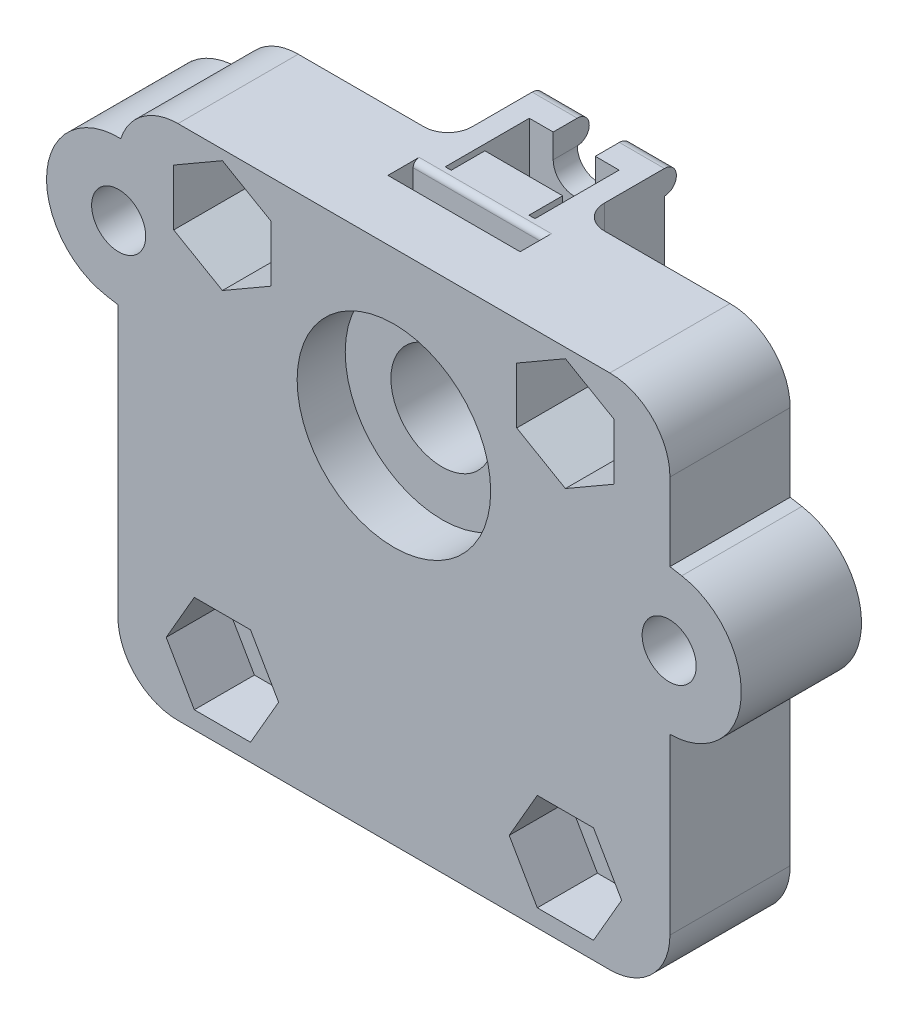
SolidWorks part; units mm, degrees
ref_plane "Front Plane" through (0, 0, 0) normal (0, 0, 1) x (1, 0, 0)
ref_plane "Top Plane" through (0, 0, 0) normal (0, 1, 0) x (1, 0, 0)
ref_plane "Right Plane" through (0, 0, 0) normal (1, 0, 0) x (0, 0, -1)
sketch "Sketch1" plane through (0, 0, 0) normal (0, 1, 0) x (1, 0, 0)
  line L0 (0, 0) -> (-22.961, -55.4328)
  line L1 (0, 0) -> (22.961, -55.4328)
  line L2 (0, 0) -> (0, -29.5283) construction
  circle A0 centre (0, 0) radius 60
  circle A1 centre (0, 0) radius 55
  circle A2 centre (0, 0) radius 50
  circle A3 centre (0, 0) radius 45
  dimension "D1" = 120
  dimension "D2" = 5
  dimension "D3" = 5
  dimension "D4" = 5
  dimension "D5" = 45
extrude "Boss-Extrude1" add sketch "Sketch1" along normal mid plane 27 contours A1 L0 A0 L1 | A2 L0 A1 L1 | A3 L0 A2 L1 region at (0, 0, 46.3313) region at (0, 0, 51.1997) region at (0, 0, 56.0688)
extrude "Boss-Extrude2" add sketch "Sketch1<3>" along normal mid plane 37 contours A2 L0 A1 L1 region at (0, 0, 51.1997)
sketch "Sketch1<3>" plane through (0, 0, 0) normal (0, 1, 0) x (1, 0, 0) same geometry as "Sketch1"
ref_plane "Plane1" through (0, 0, 60) normal (0, 0, 1) x (1, 0, 0)
sketch "Sketch3" plane through (0, 0, 0) normal (0, -1, 0) x (1, 0, 0)
  line L0 (-22.961, 55.4328) -> (-22.961, 266)
  line L1 (-22.961, 266) -> (22.961, 266)
  line L2 (22.961, 266) -> (22.961, 55.4328)
  line L3 (-17.961, 57.2486) -> (-17.961, 246)
  line L4 (-17.961, 246) -> (17.961, 246)
  line L5 (17.961, 246) -> (17.961, 57.2486)
  arc A0 (22.961, 55.4328) -> (-22.961, 55.4328) centre (0, 0) ccw construction
  arc A1 (22.961, 55.4328) -> (-22.961, 55.4328) centre (0, 0) ccw
  dimension "D1" = 5
  dimension "D2" = 5
  dimension "D3" = 20
  dimension "D4" = 266
extrude "Boss-Extrude3" add sketch "Sketch3" against normal mid plane 10 contours L3 A1 L0 L1 L2 L5 L4 region at (-20.8058, 0, 160.7164)
sketch "Sketch4" plane through (0, 0, 0) normal (0, 1, 0) x (1, 0, 0)
  line L0 (22.961, -266) -> (22.961, -55.4328) construction
  line L1 (-22.961, -266) -> (22.961, -266)
  line L2 (-22.961, -266) -> (-22.961, -246)
  line L3 (-22.961, -246) -> (22.961, -246)
  line L4 (22.961, -266) -> (22.961, -246)
  line L5 (-17.961, -246) -> (17.961, -246) construction
extrude "Boss-Extrude4" add sketch "Sketch4" along normal mid plane 27
sketch "Sketch2" plane through (0, 0, 0) normal (0, 0, 1) x (1, 0, 0)
  circle A0 centre (0, 0) radius 4.25
  dimension "D1" = 8.5
extrude "Cut-Extrude1" cut sketch "Sketch2" along normal through all
sketch "Sketch6" plane through (0, 0, 266) normal (0, 0, 1) x (1, 0, 0)
  circle A0 centre (0, 0) radius 8.05
  dimension "D1" = 16.1
extrude "Cut-Extrude3" cut sketch "Sketch6" against normal blind 14
sketch "Sketch9" plane through (0, 0, 0) normal (0, 1, 0) x (1, 0, 0)
  line L0 (-22.961, -55.4328) -> (-22.961, -68)
  line L1 (-22.961, -55.4328) -> (-22.961, -246) construction
  line L2 (-22.961, -68) -> (22.961, -68)
  line L3 (22.961, -246) -> (22.961, -55.4328) construction
  line L4 (22.961, -68) -> (22.961, -55.4328)
  arc A0 (-22.961, -55.4328) -> (22.961, -55.4328) centre (0, 0) ccw construction
  arc A1 (-22.961, -55.4328) -> (22.961, -55.4328) centre (0, 0) ccw
  point P3 (0, -60)
  dimension "D1" = 8
extrude "Boss-Extrude5" add sketch "Sketch9" along normal mid plane 27
sketch "Sketch8" plane through (0, 0, 60) normal (0, 0, 1) x (1, 0, 0)
  circle A0 centre (0, 0) radius 9
  dimension "D1" = 18
extrude "Cut-Extrude5" cut sketch "Sketch8" against normal up to next
sketch "Sketch10" plane through (0, 0, 60) normal (0, 0, 1) x (1, 0, 0)
  circle A0 centre (0, 0) radius 4
  dimension "D1" = 8
extrude "Cut-Extrude6" cut sketch "Sketch10" along normal up to next
sketch "Sketch11" plane through (0, 0, 68) normal (0, 0, 1) x (1, 0, 0)
  circle A0 centre (0, 0) radius 8
  dimension "D1" = 16
extrude "Cut-Extrude7" cut sketch "Sketch11" against normal blind 4
sketch "Sketch18" plane through (0, 0, 0) normal (0, 0, 1) x (1, 0, 0)
  circle A0 centre (0, 0) radius 11
  dimension "D1" = 22
extrude "Cut-Extrude9" cut sketch "Sketch18" along normal blind 47
sketch "Sketch19" plane through (0, 0, 0) normal (0, 1, 0) x (1, 0, 0)
  line L1 (-22.961, -68) -> (22.961, -68)
  line L2 (-22.961, -68) -> (-22.961, -266)
  line L3 (-22.961, -266) -> (22.961, -266)
  line L4 (22.961, -68) -> (22.961, -266)
sketch "Sketch20" plane through (0, 0, 0) normal (0, 1, 0) x (1, 0, 0)
  line L0 (22.961, -68) -> (22.961, -266) construction
  line L1 (-22.961, -246) -> (22.961, -246)
  line L2 (-22.961, -246) -> (-22.961, -41.5746)
  line L3 (-22.961, -41.5746) -> (22.961, -41.5746)
  line L4 (22.961, -246) -> (22.961, -41.5746)
extrude "Cut-Extrude11" cut sketch "Sketch20" against normal through all both and the other way through all
sketch "Sketch21" plane through (0, -13.5, 0) normal (0, -1, 0) x (1, 0, 0)
  line L0 (22.961, 266) -> (22.961, 246) construction
  line L1 (-22.961, 246) -> (22.961, 246)
  line L2 (-22.961, 246) -> (-22.961, 256)
  line L3 (-22.961, 256) -> (22.961, 256)
  line L4 (22.961, 246) -> (22.961, 256)
extrude "Boss-Extrude6" add sketch "Sketch21" along normal blind 16
hole_wizard "M5 Clearance Hole1" positions "Sketch22" profile "Sketch23" hole size "M5" standard "ISO" end condition through all
sketch "Sketch22" plane through (0, 0, 246) normal (0, 0, -1) x (-1, 0, 0)
  line L0 (22.961, -29.5) -> (-22.961, -29.5) construction
  line L1 (-22.961, 13.5) -> (-22.961, -29.5) construction
  point P2 (-14.2661, -24)
  dimension "D1" = 5.5
  dimension "D2" = 8.6949
sketch "Sketch23" plane through (14.2661, -24, 246) normal (1, 0, 0) x (0, 1, 0)
  line L0 (0, 0) -> (0, 20)
  line L1 (0, 20) -> (2.75, 20)
  line L2 (2.75, 20) -> (2.75, 0)
  line L5 (2.75, 0) -> (0, 0)
  line L11 (0, -6.35) -> (0, 107.95) construction
  dimension "Thru Hole Dia." = 5.5
  dimension "Thru Hole Depth" = 20
sketch "Sketch24" plane through (0, 0, 256) normal (0, 0, 1) x (1, 0, 0)
  line L1 (18.9426, -24) -> (16.6043, -19.95)
  line L2 (16.6043, -19.95) -> (11.9278, -19.95)
  line L3 (11.9278, -19.95) -> (9.5895, -24)
  line L4 (9.5895, -24) -> (11.9278, -28.05)
  line L5 (11.9278, -28.05) -> (16.6043, -28.05)
  line L6 (16.6043, -28.05) -> (18.9426, -24)
  circle A0 centre (14.2661, -24) radius 4.05 construction
  dimension "D1" = 8.1
extrude "Cut-Extrude12" cut sketch "Sketch24" against normal blind 5
mirror "Mirror1" about plane through (0, 0, 0) normal (1, 0, 0) of "M5 Clearance Hole1"
mirror "Mirror2" about plane through (0, 0, 0) normal (1, 0, 0) of "Cut-Extrude12"
pattern_linear "LPattern2" count 2 spacing 32 along (0, 1, 0) of "Mirror1"
sketch "Sketch25" plane through (0, 0, 246) normal (0, 0, -1) x (-1, 0, 0)
  line L0 (-18.3161, 10.3383) -> (-18.3161, 13.5)
  line L1 (-18.3161, 10.3383) -> (-18.3161, 5.6617)
  line L2 (-18.3161, 5.6617) -> (-14.2661, 3.3235)
  line L3 (-14.2661, 3.3235) -> (-10.2161, 5.6617)
  line L4 (-10.2161, 5.6617) -> (-10.2161, 10.3383)
  line L5 (-10.2161, 10.3383) -> (-14.2661, 12.6765)
  line L6 (-14.2661, 12.6765) -> (-18.3161, 10.3383)
  line L7 (-22.961, 13.5) -> (22.961, 13.5) construction
  line L8 (-18.3161, 13.5) -> (-10.2161, 13.5)
  line L9 (-10.2161, 13.5) -> (-10.2161, 10.3383)
  circle A0 centre (-14.2661, 8) radius 4.05 construction
  circle M7 centre (-14.2661, 8) radius 2.75
  dimension "D1" = 8.1
extrude "Cut-Extrude13" cut sketch "Sketch25" against normal through all from offset 4 contours M7 | L5 L6 L1 L2 L3 L4 M7 region at (16.2292, 11.4002, 246) region at (14.2661, 8, 246) offset against normal yes
mirror "Mirror3" about plane through (0, 0, 0) normal (1, 0, 0) of "Cut-Extrude13"
sketch "Sketch26" plane through (0, 13.5, 0) normal (0, 1, 0) x (1, 0, 0)
  line L0 (22.961, -266) -> (22.961, -246) construction
  line L1 (-22.961, -266) -> (22.961, -266)
  line L2 (-22.961, -266) -> (-22.961, -256)
  line L3 (-22.961, -256) -> (22.961, -256)
  line L4 (22.961, -266) -> (22.961, -256)
  dimension "D1" = 10
extrude "Cut-Extrude14" cut sketch "Sketch26" against normal through all
fillet "Fillet1" radius 5 4 edges at (22.961, -29.5, 251) (22.961, 13.5, 251) (-22.961, -29.5, 251) (-22.961, 13.5, 251)
sketch "Sketch30" plane through (0, 0, 246) normal (0, 0, -1) x (-1, 0, 0)
  line L1 (-5.5, 6.5) -> (5.5, 6.5)
  line L2 (-5.5, 6.5) -> (-5.5, 13.5)
  line L3 (-5.5, 13.5) -> (5.5, 13.5)
  line L4 (5.5, 6.5) -> (5.5, 13.5)
  line L5 (-5.5, 6.5) -> (5.5, 13.5) construction
  line L6 (-5.5, 13.5) -> (5.5, 6.5) construction
  line L7 (-17.961, 13.5) -> (17.961, 13.5) construction
  point P0 (0, 10)
  dimension "D1" = 11
  dimension "D2" = 7
extrude "Boss-Extrude8" add sketch "Sketch30" along normal blind 5
sketch "Sketch31" plane through (0, 13.5, 0) normal (0, 1, 0) x (1, 0, 0)
  line L0 (3.735, -241) -> (3.735, -248)
  line L1 (-5.5, -241) -> (5.5, -241) construction
  line L2 (3.735, -248) -> (3.235, -248)
  line L3 (3.235, -248) -> (3.235, -245.2)
  line L4 (3.235, -245.2) -> (-3.235, -245.2)
  line L5 (-3.235, -245.2) -> (-3.235, -248)
  line L6 (-3.235, -248) -> (-3.735, -248)
  line L7 (-3.735, -248) -> (-3.735, -241)
  line L8 (-3.735, -241) -> (3.735, -241)
  line L9 (0, -256) -> (0, -239.8104) construction
  dimension "D1" = 0.5
  dimension "D2" = 7.47
  dimension "D3" = 7
  dimension "D4" = 4.2
extrude "Cut-Extrude15" cut sketch "Sketch31" against normal blind 5
fillet "Fillet3" radius 2 3 edges at (-5.5, 10, 246) (0, 6.5, 246) (5.5, 10, 246)
sketch "Sketch32" plane through (0, 0, 241) normal (0, 0, -1) x (-1, 0, 0)
  line L0 (-1.75, 11.5) -> (-1.75, 13.5)
  line L1 (-5.5, 6.5) -> (5.5, 6.5)
  line L2 (-5.5, 6.5) -> (-5.5, 13.5)
  line L3 (-5.5, 13.5) -> (5.5, 13.5)
  line L4 (5.5, 6.5) -> (5.5, 13.5)
  line L5 (1.75, 11.5) -> (1.75, 13.5)
  circle A0 centre (0, 11.5) radius 1.75
  line M6 (3.735, 8.5) -> (-3.735, 8.5)
  line M7 (-3.735, 8.5) -> (-3.735, 13.5)
  line M8 (-3.735, 13.5) -> (-5.5, 13.5)
  line M9 (-5.5, 13.5) -> (-5.5, 6.5)
  line M10 (-5.5, 6.5) -> (5.5, 6.5)
  line M11 (5.5, 6.5) -> (5.5, 13.5)
  line M12 (5.5, 13.5) -> (3.735, 13.5)
  line M13 (3.735, 13.5) -> (3.735, 8.5)
  dimension "D1" = 3.5
  dimension "D2" = 5
extrude "Boss-Extrude9" add sketch "Sketch32" along normal blind 2 contours M13 M6 M7 M8 M9 M10 M11 M12 | A0 L0 L3 L5 M7 M6 M13 region at (0, 9.6601, 241) region at (3.8654, 11, 241)
sketch "Sketch34" plane through (-5.5, 0, 0) normal (-1, 0, 0) x (0, 0, 1)
  line L0 (239, 13.5) -> (239, 11.5)
  line L1 (239, 6.5) -> (239, 13.5) construction
  arc A0 (239, 11.5) -> (239, 13.5) centre (239, 12.5) cw
  dimension "D1" = 1
extrude "Boss-Extrude10" add sketch "Sketch34" against normal blind 3.75
mirror "Mirror5" about plane through (0, 0, 0) normal (1, 0, 0) of "Boss-Extrude10"
sketch "Sketch36" plane through (0, 13.5, 0) normal (0, 1, 0) x (1, 0, 0)
  line L1 (-5.5, -251) -> (5.5, -251)
  line L2 (-5.5, -251) -> (-5.5, -248.9)
  line L3 (-5.5, -248.9) -> (5.5, -248.9)
  line L4 (5.5, -251) -> (5.5, -248.9)
  line L5 (-5.5, -239) -> (-5.5, -244) construction
  line L6 (5.5, -239) -> (5.5, -244) construction
  line L7 (-7.5, -246) -> (-17.961, -246) construction
  dimension "D1" = 2.1
  dimension "D2" = 5
extrude "Cut-Extrude17" cut sketch "Sketch36" against normal blind 2.5
fillet "Fillet4" radius 0.5 1 edges at (0, 13.5, 248.9)
sketch "Sketch38" plane through (0, 0, 256) normal (0, 0, 1) x (1, 0, 0)
  line L0 (-22.8968, 4.0373) -> (22.8968, -4.0373) construction
  line L1 (-21.8549, 9.9462) -> (23.9387, 1.8715)
  line L2 (-23.9387, -1.8715) -> (21.8549, -9.9462)
  line L3 (0, 0) -> (-47.77, 0) construction
  line L4 (22.961, -24.5) -> (22.961, 8.5) construction
  line L5 (17.961, 13.5) -> (-17.961, 13.5) construction
  line L6 (-22.961, -24.5) -> (-22.961, 8.5) construction
  line L7 (22.961, -24.5) -> (22.961, 8.5)
  line L8 (17.961, 13.5) -> (-17.961, 13.5)
  line L9 (-22.961, -24.5) -> (-22.961, 8.5)
  arc A0 (-21.8549, 9.9462) -> (-23.9387, -1.8715) centre (-22.8968, 4.0373) ccw
  arc A1 (21.8549, -9.9462) -> (23.9387, 1.8715) centre (22.8968, -4.0373) ccw
  arc A2 (22.961, 8.5) -> (17.961, 13.5) centre (17.961, 8.5) ccw construction
  arc A3 (-17.961, 13.5) -> (-22.961, 8.5) centre (-17.961, 8.5) ccw construction
  arc A4 (22.961, 8.5) -> (17.961, 13.5) centre (17.961, 8.5) ccw
  arc A5 (-17.961, 13.5) -> (-22.961, 8.5) centre (-17.961, 8.5) ccw
  point P2 (0, 0)
  line M9 (22.961, -24.5) -> (22.961, 8.5)
  arc M12 (-17.961, 13.5) -> (-22.961, 8.5) centre (-17.961, 8.5) ccw
  line M13 (-22.961, 8.5) -> (-22.961, -24.5)
  dimension "D3" = 6
  dimension "D1" = 10
  dimension "D2" = 46.5
extrude "Boss-Extrude11" add sketch "Sketch38" against normal up to surface (10 mm away) contours L1 A0 L2 M13 M12 | L2 A1 L1 M9 region at (25.4769, -4.0344, 256) region at (-25.4712, 4.0468, 256) up to face at (0, -2.3333, 246)
sketch "Sketch39" plane through (0, 0, 246) normal (0, 0, -1) x (-1, 0, 0)
  line L1 (-22.8968, -8.1076) -> (-19.3718, -6.0725)
  line L2 (-19.3718, -6.0725) -> (-19.3718, -2.0022)
  line L3 (-19.3718, -2.0022) -> (-22.8968, 0.033)
  line L4 (-22.8968, 0.033) -> (-26.4218, -2.0022)
  line L5 (-26.4218, -2.0022) -> (-26.4218, -6.0725)
  line L6 (-26.4218, -6.0725) -> (-22.8968, -8.1076)
  line L7 (18.8943, 3.2973) -> (21.5364, 0.2011)
  line L8 (21.5364, 0.2011) -> (25.5389, 0.941)
  line L9 (25.5389, 0.941) -> (26.8993, 4.7773)
  line L10 (26.8993, 4.7773) -> (24.2572, 7.8736)
  line L11 (24.2572, 7.8736) -> (20.2547, 7.1336)
  line L12 (20.2547, 7.1336) -> (18.8943, 3.2973)
  line L15 (19.5745, 5.2155) -> (18.3161, 5.6617) construction
  circle A0 centre (-22.8968, -4.0373) radius 3.525 construction
  circle A1 centre (22.8968, 4.0373) radius 3.525 construction
  dimension "D1" = 7.05
extrude "Cut-Extrude18" cut sketch "Sketch39" against normal blind 4
hole_wizard "M4 Clearance Hole1" positions "Sketch40" profile "Sketch41" hole size "M4" standard "ISO" end condition through all
sketch "Sketch40" plane through (0, 0, 256) normal (0, 0, 1) x (1, 0, 0)
  point P0 (-22.8968, 4.0373)
  point P3 (22.8968, -4.0373)
sketch "Sketch41" plane through (-22.8968, 4.0373, 256) normal (1, 0, 0) x (0, -1, 0)
  line L0 (0, 0) -> (0, 18)
  line L1 (0, 18) -> (2.25, 18)
  line L2 (2.25, 18) -> (2.25, 0)
  line L5 (2.25, 0) -> (0, 0)
  line L11 (0, -6.35) -> (0, 107.95) construction
  dimension "Thru Hole Dia." = 4.5
  dimension "Thru Hole Depth" = 18
